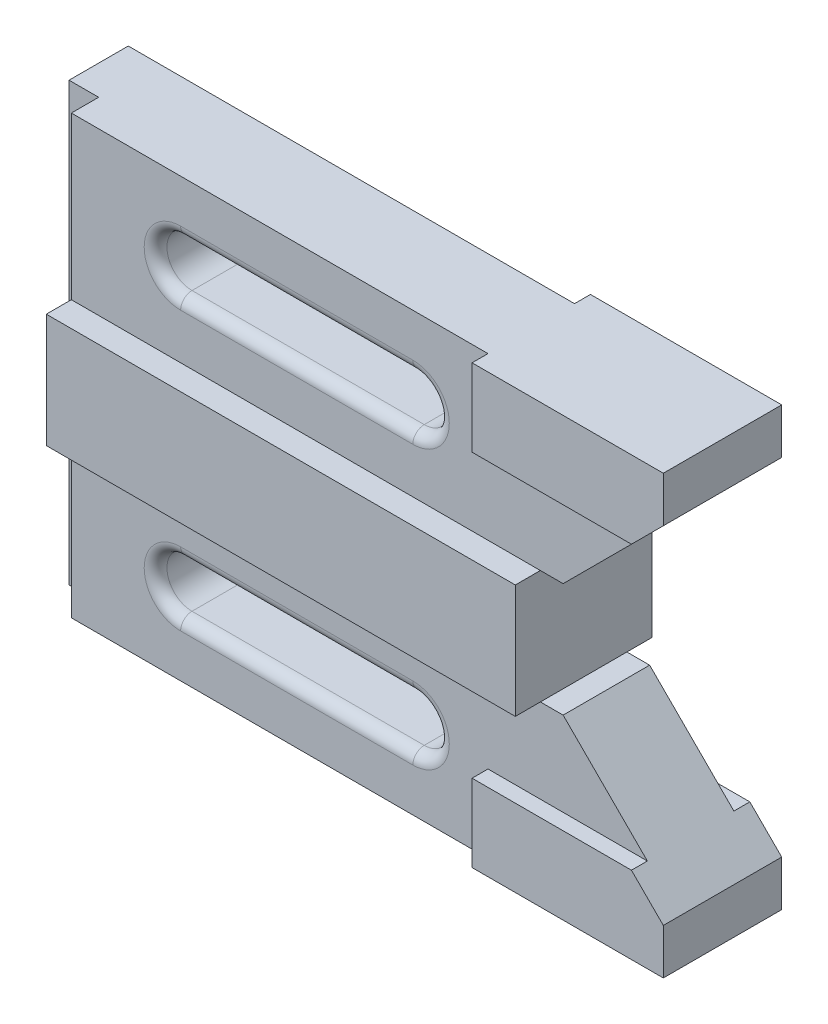
SolidWorks part; units mm, degrees
material "1060 Alloy"
ref_plane "Front Plane" through (0, 0, 0) normal (0, 0, 1) x (1, 0, 0)
ref_plane "Top Plane" through (0, 0, 0) normal (0, 1, 0) x (1, 0, 0)
ref_plane "Right Plane" through (0, 0, 0) normal (1, 0, 0) x (0, 0, -1)
sketch "Sketch2" plane through (0, 0, 0) normal (0, 0, 1) x (1, 0, 0)
  line L0 (0, 0) -> (0, 48)
  line L1 (0, 48) -> (140, 48)
  line L2 (0, 0) -> (109.5, 0)
  line L3 (109.5, 0) -> (109.5, 12.5)
  line L4 (109.5, 12.5) -> (114.5, 12.5)
  line L5 (114.5, 12.5) -> (140, 38)
  line L6 (140, 38) -> (140, 48)
  line L7 (109.5, 12.5) -> (0, 12.5)
  line L8 (98, 48) -> (98, 31)
  line L9 (98, 31) -> (133, 31)
  line L10 (0, 30.5) -> (30.5, 30.5)
  line L11 (30.5, 30.5) -> (81.5, 30.5) construction
  line L12 (30.5, 36) -> (81.5, 36)
  line L13 (30.5, 25) -> (81.5, 25)
  arc A0 (30.5, 36) -> (30.5, 25) centre (30.5, 30.5) ccw
  arc A1 (81.5, 25) -> (81.5, 36) centre (81.5, 30.5) ccw
  point P14 (56, 30.5)
  dimension "D12" = 5.5
  dimension "D1" = 140
  dimension "D2" = 48
  dimension "D3" = 10
  dimension "D4" = 45
  dimension "D5" = 35.5
  dimension "D6" = 30.5
  dimension "D7" = 35
  dimension "D8" = 17
  dimension "D9" = 17.5
  dimension "D10" = 30.5
  dimension "D11" = 51
extrude "Boss-Extrude1" add sketch "Sketch2" along normal mid plane 30 contours L3 L7 L0 L2 region at (54.75, 6.25, 0)
extrude "Boss-Extrude2" add sketch "Sketch2<3>" along normal mid plane 26 separate body contours L8 L9 L5 L6 L1 region at (118.3367, 39.7191, 0)
sketch "Sketch2<3>" plane through (0, 0, 0) normal (0, 0, 1) x (1, 0, 0) same geometry as "Sketch2"
extrude "Boss-Extrude3" add sketch "Sketch2<4>" along normal mid plane 19 contours A1 L13 A0 L0 L7 L4 L5 L9 L8 L1 L12 region at (1.3766, 21.5, 0)
sketch "Sketch2<4>" plane through (0, 0, 0) normal (0, 0, 1) x (1, 0, 0) same geometry as "Sketch2"
sketch "Sketch3" plane through (0, 48, 0) normal (0, 1, 0) x (1, 0, 0)
  line L1 (0, -15) -> (6.5, -15)
  line L2 (0, -15) -> (0, -3.5)
  line L3 (0, -3.5) -> (6.5, -3.5)
  line L4 (6.5, -15) -> (6.5, -3.5)
  dimension "D1" = 6.5
  dimension "D2" = 11.5
extrude "Cut-Extrude1" cut sketch "Sketch3" against normal through all both and the other way through all
mirror "Mirror1" about plane through (0, 0, 15) normal (0, 1, 0) of bodies 104
fillet "Fillet2" radius 2.5 16 edges at (56, -25, 9.5) (56, 36, 9.5) (87, 30.5, -9.5) (56, 36, -9.5) (56, 25, -9.5) (25, 30.5, -9.5) (87, 30.5, 9.5) (25, 30.5, 9.5) (56, 25, 9.5) (56, -25, -9.5) (87, -30.5, -9.5) (56, -36, -9.5) (25, -30.5, -9.5) (87, -30.5, 9.5) (25, -30.5, 9.5) (56, -36, 9.5)
equation "\"A\"= 140mm"
equation "\"B\"= 51"
equation "\"C\"= 45deg"
equation "\"D1@Sketch2\"=\"A\""
equation "\"D11@Sketch2\"=\"B\""
